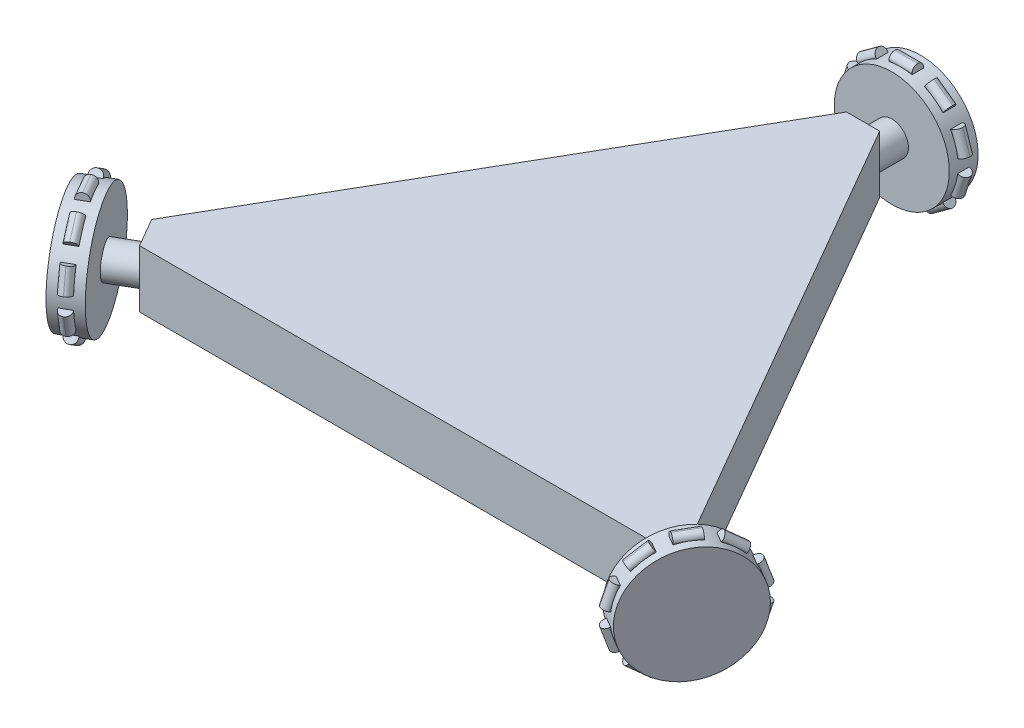
SolidWorks part; units mm, degrees
ref_plane "Alzado" through (0, 0, 0) normal (0, 0, 1) x (1, 0, 0)
ref_plane "Planta" through (0, 0, 0) normal (0, 1, 0) x (1, 0, 0)
ref_plane "Vista lateral" through (0, 0, 0) normal (1, 0, 0) x (0, 0, -1)
sketch "Croquis1" plane through (0, 0, 0) normal (0, 1, 0) x (1, 0, 0)
  line L0 (-44.2265, -36.8929) -> (44.2265, -36.8929)
  line L1 (47.1132, -31.8929) -> (2.8868, 44.7097)
  line L3 (-2.8868, 44.7097) -> (-47.1132, -31.8929)
  line L4 (-47.1132, -31.8929) -> (-44.2265, -36.8929)
  line L5 (44.2265, -36.8929) -> (47.1132, -31.8929)
  line L6 (-2.8868, 44.7097) -> (2.8868, 44.7097)
  dimension "D1" = 60
  dimension "D2" = 60
  dimension "D5" = 60
  dimension "D6" = 60
extrude "Saliente-Extruir1" add sketch "Croquis1" along normal blind 10
sketch "Croquis2" plane through (49.145, 0, 28.3739) normal (0.866, 0, 0.5) x (0.5, 0, -0.866)
  circle A0 centre (-6.9502, 5) radius 2.8868
extrude "Saliente-Extruir2" add sketch "Croquis2" along normal blind 5
sketch "Croquis3" plane through (-49.145, 0, 28.3739) normal (-0.866, 0, 0.5) x (0.5, 0, 0.866)
  circle A0 centre (6.9502, 5) radius 2.8868
extrude "Saliente-Extruir3" add sketch "Croquis3" along normal blind 5
sketch "Croquis4" plane through (0, 0, -44.7097) normal (0, 0, -1) x (-1, 0, 0)
  line L0 (0, 5.5) -> (0, -5.5) construction
  circle A0 centre (0, 5) radius 2.8868
extrude "Saliente-Extruir4" add sketch "Croquis4" along normal blind 5
sketch "Croquis5" plane through (-53.4751, 0, 30.8739) normal (-0.866, 0, 0.5) x (0.5, 0, 0.866)
  circle A0 centre (6.9502, 5) radius 10
  dimension "D1" = 20
extrude "Saliente-Extruir5" add sketch "Croquis5" along normal blind 5
ref_axis "Eje1" through (0, 16, 0) along (0, -1, 0)
ref_plane "Plano1" through (-55.6401, 0, 32.1239) normal (-0.866, 0, 0.5) x (0.5, 0, 0.866)
sketch "Croquis6" plane through (-55.6401, 0, 32.1239) normal (-0.866, 0, 0.5) x (0.5, 0, 0.866)
  line L1 (4.9502, 14) -> (8.9502, 14)
  line L2 (4.9502, 14) -> (4.9502, 16)
  line L3 (4.9502, 16) -> (8.9502, 16)
  line L4 (8.9502, 14) -> (8.9502, 16)
  line L5 (4.9502, 14) -> (8.9502, 16) construction
  line L6 (4.9502, 16) -> (8.9502, 14) construction
  circle A0 centre (6.9502, 5) radius 10 construction
  point P0 (6.9502, 15)
  dimension "D1" = 4
  dimension "D2" = 2
extrude "Saliente-Extruir6" add sketch "Croquis6" along normal blind 1 and the other way blind 1
fillet "Redondeo1" radius 1 2 edges at (-51.299, 16, 37.6429) (-53.0311, 16, 38.6429)
ref_axis "Eje2" through (-53.2476, 5, 38.7679) along (0.866, 0, -0.5)
pattern_circular "MatrizC1" count 10 over 360 about axis through (-53.2476, 5, 38.7679) along (0.866, 0, -0.5) of "Saliente-Extruir6", "Redondeo1"
sketch "Croquis7" plane through (0, 0, -49.7097) normal (0, 0, -1) x (-1, 0, 0)
  circle A0 centre (0, 5) radius 10
  dimension "D1" = 20
extrude "Saliente-Extruir7" add sketch "Croquis7" along normal blind 5 contours A0
sketch "Croquis8" plane through (53.4751, 0, 30.8739) normal (0.866, 0, 0.5) x (0.5, 0, -0.866)
  circle A0 centre (-6.9502, 5) radius 10
  dimension "D1" = 20
extrude "Saliente-Extruir8" add sketch "Croquis8" along normal blind 5
ref_plane "Plano2" through (55.6401, 0, 32.1239) normal (0.866, 0, 0.5) x (0.5, 0, -0.866)
ref_plane "Plano3" through (0, 0, -52.2097) normal (0, 0, -1) x (-1, 0, 0)
sketch "Croquis9" plane through (0, 0, -52.2097) normal (0, 0, -1) x (-1, 0, 0)
  line L0 (0, 12.1) -> (0, -12.1) construction
  line L1 (-2, 14) -> (2, 14)
  line L2 (-2, 14) -> (-2, 16)
  line L3 (-2, 16) -> (2, 16)
  line L4 (2, 14) -> (2, 16)
  line L5 (-2, 14) -> (2, 16) construction
  line L6 (-2, 16) -> (2, 14) construction
  circle A0 centre (0, 5) radius 10 construction
  point P0 (0, 15)
  dimension "D1" = 4
  dimension "D2" = 2
extrude "Saliente-Extruir9" add sketch "Croquis9" along normal blind 1 and the other way blind 1
fillet "Redondeo2" radius 1 2 edges at (0, 16, -51.2097) (0, 16, -53.2097)
ref_axis "Eje3" through (0, 5, -54.7097) along (0, 0, 1)
pattern_circular "MatrizC2" count 10 over 360 about axis through (0, 5, -54.7097) along (0, 0, 1) of "Saliente-Extruir9", "Redondeo2"
sketch "Croquis10" plane through (55.6401, 0, 32.1239) normal (0.866, 0, 0.5) x (0.5, 0, -0.866)
  line L1 (-8.9502, 14) -> (-4.9502, 14)
  line L2 (-8.9502, 14) -> (-8.9502, 16)
  line L3 (-8.9502, 16) -> (-4.9502, 16)
  line L4 (-4.9502, 14) -> (-4.9502, 16)
  line L5 (-8.9502, 14) -> (-4.9502, 16) construction
  line L6 (-8.9502, 16) -> (-4.9502, 14) construction
  circle A0 centre (-6.9502, 5) radius 10 construction
  point P0 (-6.9502, 15)
  dimension "D1" = 4
  dimension "D2" = 2
extrude "Saliente-Extruir10" add sketch "Croquis10" along normal blind 1 and the other way blind 1
fillet "Redondeo3" radius 1 2 edges at (51.299, 16, 37.6429) (53.0311, 16, 38.6429)
ref_axis "Eje4" through (61.8301, 5, 43.723) along (-0.866, 0, -0.5)
pattern_circular "MatrizC3" count 10 over 360 about axis through (61.8301, 5, 43.723) along (-0.866, 0, -0.5) of "Saliente-Extruir10", "Redondeo3"
